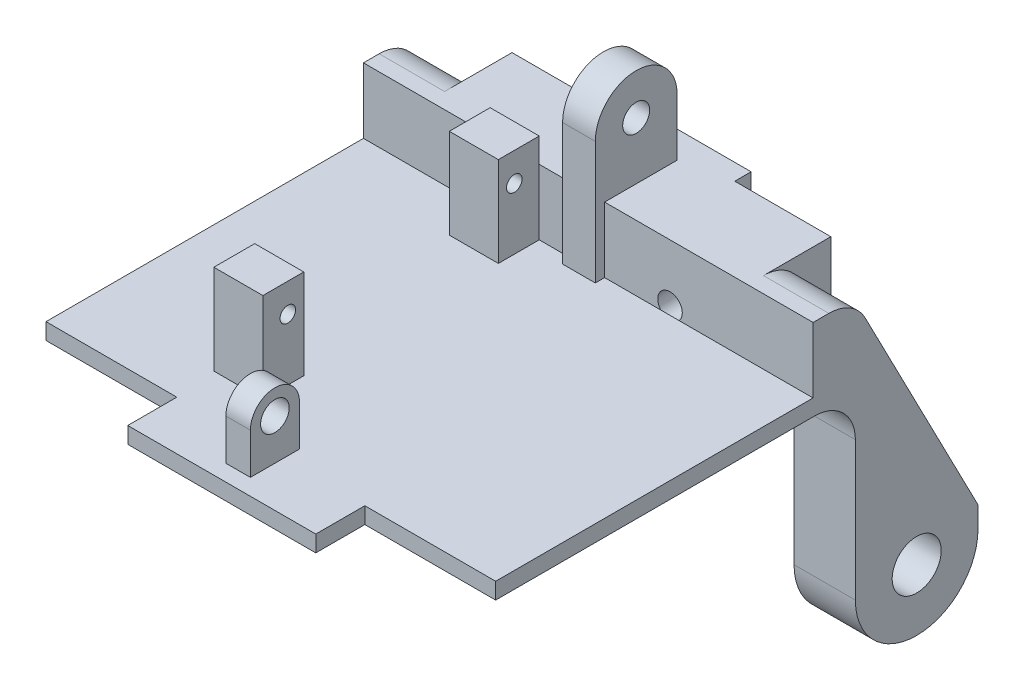
SolidWorks part; units mm, degrees
ref_plane "前视基准面" through (0, 0, 0) normal (0, 0, 1) x (1, 0, 0)
ref_plane "上视基准面" through (0, 0, 0) normal (0, 1, 0) x (1, 0, 0)
ref_plane "右视基准面" through (0, 0, 0) normal (1, 0, 0) x (0, 0, -1)
sketch "草图1" plane through (0, 0, 0) normal (0, 1, 0) x (1, 0, 0)
  line L1 (-27.5, -19.5) -> (27.5, -19.5)
  line L2 (-27.5, -19.5) -> (-27.5, 19.5)
  line L3 (-27.5, 19.5) -> (27.5, 19.5)
  line L4 (27.5, -19.5) -> (27.5, 19.5)
  line L5 (-27.5, -19.5) -> (27.5, 19.5) construction
  line L6 (-27.5, 19.5) -> (27.5, -19.5) construction
  point P0 (0, 0)
  dimension "D1" = 55
  dimension "D2" = 39
extrude "凸台-拉伸1" add sketch "草图1" along normal blind 2
sketch "草图2" plane through (0, 2, 0) normal (0, 1, 0) x (1, 0, 0)
  line L0 (-27.5, -19.5) -> (27.5, -19.5) construction
  line L1 (-11.5, -19.5) -> (11.5, -19.5)
  line L2 (-11.5, -19.5) -> (-11.5, -25.5)
  line L3 (-11.5, -25.5) -> (11.5, -25.5)
  line L4 (11.5, -19.5) -> (11.5, -25.5)
  line L5 (27.5, 19.5) -> (-27.5, 19.5) construction
  point P9 (0, -25.5)
  dimension "D1" = 23
  dimension "D2" = 45
extrude "凸台-拉伸2" add sketch "草图2" against normal blind 2
sketch "草图3" plane through (0, 2, 0) normal (0, 1, 0) x (1, 0, 0)
  line L1 (-6, -14.471) -> (-12, -14.471)
  line L2 (-6, -14.471) -> (-6, -9.471)
  line L3 (-6, -9.471) -> (-12, -9.471)
  line L4 (-12, -14.471) -> (-12, -9.471)
  line L6 (-6, 14.329) -> (-12, 14.329)
  line L7 (-6, 14.329) -> (-6, 19.329)
  line L8 (-6, 19.329) -> (-12, 19.329)
  line L9 (-12, 14.329) -> (-12, 19.329)
  dimension "D1" = 6
  dimension "D2" = 23.8
  dimension "D3" = 6
  dimension "D4" = 6
  dimension "D5" = 6
  dimension "D6" = 5
  dimension "D7" = 5
extrude "凸台-拉伸3" add sketch "草图3" along normal blind 11
sketch "草图5" plane through (-12, 0, 0) normal (-1, 0, 0) x (0, 0, 1)
  line L0 (-14.329, 13) -> (-14.329, 2) construction
  line L1 (9.471, 13) -> (9.471, 2) construction
  line L2 (-19.5, 2) -> (19.5, 2) construction
  line L3 (9.471, 2) -> (14.471, 2) construction
  circle A0 centre (-16.279, 9.5) radius 0.95
  circle A1 centre (11.421, 9.5) radius 0.95
  dimension "D1" = 1.95
  dimension "D2" = 1.95
  dimension "D3" = 7.5
  dimension "D4" = 7.5
  dimension "D5" = 27.7
  dimension "D6" = 1.9
  dimension "D7" = 1.9
extrude "切除-拉伸1" cut sketch "草图5" against normal blind 11
sketch "草图6" plane through (0, 2, 0) normal (0, 1, 0) x (1, 0, 0)
  line L0 (27.5, -19.5) -> (27.5, 19.5) construction
  line L1 (-27.5, 19.5) -> (27.5, 19.5)
  line L2 (-27.5, 19.5) -> (-27.5, 19.329)
  line L3 (-27.5, 19.329) -> (27.5, 19.329)
  line L4 (27.5, 19.5) -> (27.5, 19.329)
  line L5 (-6, 19.329) -> (-12, 19.329) construction
extrude "凸台-拉伸4" add sketch "草图6" along normal blind 8
sketch "草图8" plane through (0, 0, 0) normal (1, 0, 0) x (0, 0, -1)
  line L0 (28.1899, 17) -> (28.1899, 0)
  line L1 (-19.5, 2) -> (19.329, 2) construction
  line L2 (18.1899, 17) -> (18.1899, 0)
  line L4 (18.1899, 0) -> (28.1899, 0)
  line L7 (-19.5, 0) -> (19.5, 0) construction
  arc A0 (28.1899, 17) -> (18.1899, 17) centre (23.1899, 17) ccw
  circle A1 centre (23.1899, 17) radius 1.65
  dimension "D1" = 15
  dimension "D2" = 10
  dimension "D3" = 3.3
extrude "凸台-拉伸6" add sketch "草图8" along normal mid plane 4
sketch "草图10" plane through (0, 2, 0) normal (0, 1, 0) x (1, 0, 0)
  line L0 (-11.5, -25.5) -> (11.5, -25.5) construction
  line L1 (-1.5, -17.5) -> (1.5, -17.5)
  line L2 (-1.5, -17.5) -> (-1.5, -23.5)
  line L3 (-1.5, -23.5) -> (1.5, -23.5)
  line L4 (1.5, -17.5) -> (1.5, -23.5)
  point P7 (0, -17.5)
  dimension "D1" = 2
  dimension "D2" = 3
  dimension "D3" = 6
extrude "凸台-拉伸7" add sketch "草图10" along normal blind 8
sketch "草图11" plane through (0, 0, -19.329) normal (0, 0, 1) x (1, 0, 0)
  line L0 (-2, 10) -> (-27.5, 10) construction
  circle A0 centre (-10, 3) radius 1.5
  dimension "D1" = 10
  dimension "D2" = 3
  dimension "D3" = 7
extrude "切除-拉伸3" cut sketch "草图11" against normal blind 13
sketch "草图12" plane through (-27.5, 0, 0) normal (-1, 0, 0) x (0, 0, 1)
  line L1 (-19.5, 0) -> (4.0888, 0)
  line L2 (-19.5, 0) -> (19.5, 0) construction
  line L3 (-19.5, 10) -> (-19.5, 0) construction
  line L4 (-39.5, -22) -> (-39.5, 10)
  line L5 (-19.5, 10) -> (-39.5, 10)
  line L6 (-24.5, -22) -> (-24.5, 0)
  line L7 (-24.5, 0) -> (-19.5, 0)
  line L8 (-19.5, 10) -> (-19.5, 0)
  arc A0 (-39.5, -22) -> (-24.5, -22) centre (-32, -22) ccw
  circle A2 centre (-32, -22) radius 3
  line M7 (-19.5, 10) -> (-19.5, 0)
  dimension "D1" = 15
  dimension "D5" = 6
  dimension "D2" = 22
  dimension "D3" = 12.5
extrude "凸台-拉伸8" add sketch "草图12" against normal blind 7.5 contours L4 A0 L6 L7 L5 A2 M7 region at (-27.5, -7.1737, -31.1527)
sketch "草图13" plane through (0, 0, 0) normal (0, -1, 0) x (1, 0, 0)
  line L0 (-11.5, 25.5) -> (11.5, 25.5) construction
  line L1 (-5, 21) -> (5, 21)
  line L2 (-5, 21) -> (-5, 17.3)
  line L3 (-5, 17.3) -> (5, 17.3)
  line L4 (5, 21) -> (5, 17.3)
  line L5 (-5, 21) -> (5, 17.3) construction
  line L6 (-5, 17.3) -> (5, 21) construction
  point P0 (0, 19.15)
  dimension "D1" = 10
  dimension "D2" = 4.5
  dimension "D3" = 3.7
extrude "凸台-拉伸9" add sketch "草图13" along normal blind 1
mirror "镜向1" about plane through (0, 0, 0) normal (1, 0, 0) of "凸台-拉伸8", "切除-拉伸3"
fillet "圆角3" 2 edges at (0, 10, 17.5) (0, 10, 23.5) type full round first side face at (0, 6, 17.5) second side face at (0, 6, 23.5) middle face at (0, 10, 20.5)
sketch "草图15" plane through (-1.5, 0, 0) normal (-1, 0, 0) x (0, 0, 1)
  circle A0 centre (20.5, 7) radius 1.75
  dimension "D1" = 3.5
extrude "切除-拉伸5" cut sketch "草图15" against normal blind 23
sketch "草图16" plane through (0, 0, -19.5) normal (0, 0, -1) x (-1, 0, 0)
  line L0 (-20, 10) -> (-2, 10) construction
  line L1 (-7.75, 10) -> (7.75, 10)
  line L2 (-7.75, 10) -> (-7.75, 6)
  line L3 (-7.75, 6) -> (7.75, 6)
  line L4 (7.75, 10) -> (7.75, 6)
  point P6 (0, 6)
  dimension "D1" = 15.5
  dimension "D2" = 4
extrude "凸台-拉伸10" add sketch "草图16" along normal blind 20
sketch "草图17" plane through (0, 0, -19.5) normal (0, 0, -1) x (-1, 0, 0)
  line L6 (-20, 0) -> (-2, 0)
  line L7 (-20, 0) -> (-2, 0)
  line L8 (-20, 10) -> (-20, 0)
  line L10 (-7.75, 6) -> (-7.75, 10)
  line L11 (-7.75, 10) -> (-20, 10)
  line L12 (-2, 0) -> (-2, 6)
  line L14 (-2, 0) -> (-2, 6)
  line L15 (-7.75, 6) -> (-7.75, 10)
  line L16 (-2, 6) -> (-7.75, 6)
  line L18 (-2, 6) -> (-7.75, 6)
  line L21 (-7.75, 10) -> (-20, 10)
  line L32 (-20, 10) -> (-20, 0)
  line L33 (7.75, 6) -> (2, 6)
  line L34 (2, 6) -> (2, 0)
  line L35 (2, 0) -> (20, 0)
  line L36 (20, 0) -> (20, 10)
  line L37 (20, 10) -> (7.75, 10)
  line L38 (7.75, 10) -> (7.75, 6)
  line L39 (7.75, 6) -> (2, 6)
  line L40 (2, 6) -> (2, 0)
  line L41 (2, 0) -> (20, 0)
  line L42 (20, 0) -> (20, 10)
  line L43 (20, 10) -> (7.75, 10)
  line L44 (7.75, 10) -> (7.75, 6)
  circle A0 centre (10, 3) radius 1.5 construction
  circle A1 centre (-10, 3) radius 1.5 construction
  circle A2 centre (10, 3) radius 1.5
  circle A3 centre (-10, 3) radius 1.5
  dimension "D1" = 0
  dimension "D2" = 0
extrude "凸台-拉伸11" add sketch "草图17" along normal blind 10
fillet "圆角4" radius 10 2 edges at (23.75, 10, -39.5) (-23.75, 10, -39.5)
sketch "草图18" plane through (0, 10, 0) normal (0, 1, 0) x (1, 0, 0)
  line L0 (-7.75, 39.5) -> (7.75, 39.5) construction
  line L1 (-14.1233, 41.9545) -> (12.4415, 41.9545)
  line L2 (-14.1233, 41.9545) -> (-14.1233, 31.5)
  line L3 (-14.1233, 31.5) -> (12.4415, 31.5)
  line L4 (12.4415, 41.9545) -> (12.4415, 31.5)
  dimension "D1" = 8
extrude "切除-拉伸6" cut sketch "草图18" against normal blind 10
sketch "草图19" plane through (27.5, 0, 0) normal (1, 0, 0) x (0, 0, -1)
  line L0 (24.3, 10) -> (39.5, -19.3956)
  line L1 (39.5, -22) -> (39.5, 0) construction
  line L2 (24.3, 10) -> (39.5, 10)
  line L3 (39.5, 10) -> (39.5, -19.3956)
  dimension "D1" = 15.2
extrude "切除-拉伸7" cut sketch "草图19" against normal blind 8
sketch "草图20" plane through (-27.5, 0, 0) normal (-1, 0, 0) x (0, 0, 1)
  line L0 (-24.3, 10) -> (-39.5, 10)
  line L1 (-39.5, 10) -> (-39.5, -19.3956)
  line L8 (-39.5, -19.3956) -> (-39.5, -22)
  line L9 (-24.3, 10) -> (-39.5, -19.3956)
  line L10 (-19.329, 10) -> (-24.3, 10)
  line L11 (-19.329, 2) -> (-19.329, 10)
  line L12 (19.5, 2) -> (-19.329, 2)
  line L13 (19.5, 0) -> (19.5, 2)
  line L14 (-24.5, 0) -> (19.5, 0)
  line L15 (-24.5, -22) -> (-24.5, 0)
  line L17 (-24.3, 10) -> (-39.5, -19.3956)
  arc A1 (-39.5, -22) -> (-24.5, -22) centre (-32, -22) ccw
  dimension "D1" = 0
extrude "切除-拉伸8" cut sketch "草图20" against normal blind 8
fillet "圆角6" radius 5 4 edges at (23.75, 0, -24.5) (-23.75, 0, -24.5) (23.5, 10, -24.3) (-23.5, 10, -24.3)
sketch "草图22" plane through (0, -1, 0) normal (0, -1, 0) x (1, 0, 0)
  line L0 (-11.5, 25.5) -> (11.5, 25.5) construction
  line L2 (-27.5, -19.5) -> (-27.5, 19.5) construction
  circle A0 centre (0, 19.15) radius 1.4
  point P6 (-14.553, 25.3582)
  dimension "D1" = 2.8
  dimension "D2" = 6.35
  dimension "D3" = 27.5
extrude "切除-拉伸10" cut sketch "草图22" against normal blind 4
